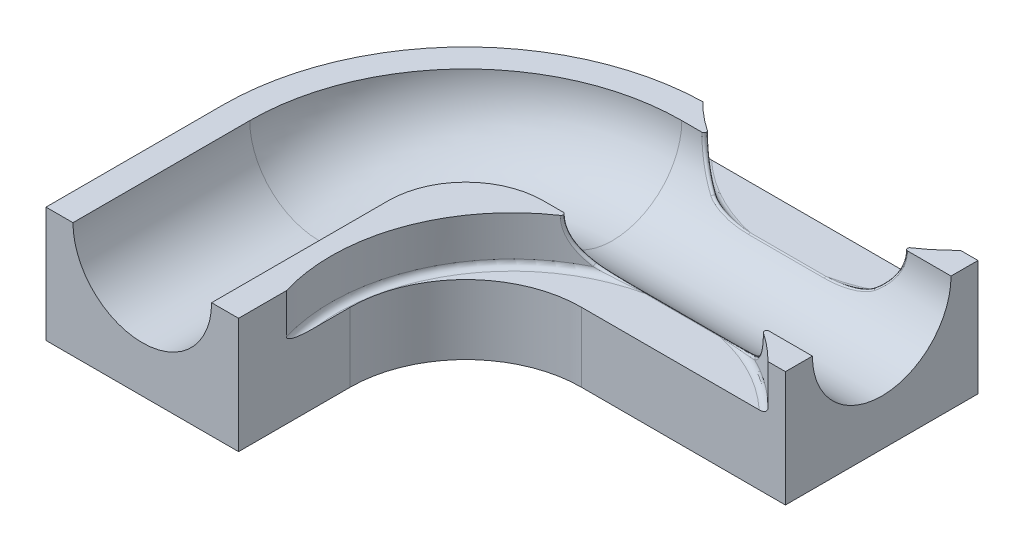
SolidWorks part; units mm, degrees
material "PLA"
ref_plane "前视基准面" through (0, 0, 0) normal (0, 0, 1) x (1, 0, 0)
ref_plane "上视基准面" through (0, 0, 0) normal (0, 1, 0) x (1, 0, 0)
ref_plane "右视基准面" through (0, 0, 0) normal (1, 0, 0) x (0, 0, -1)
sketch "草图1" plane through (0, 0, 0) normal (0, 1, 0) x (1, 0, 0)
  line L0 (0, 0) -> (-34.9545, 0) construction
  line L1 (-54, -19.0455) -> (-54, -42) construction
  line L2 (-66.5, -42) -> (-41.5, -42)
  line L3 (-41.5, -42) -> (-41.5, -27.5)
  line L4 (-66.5, -42) -> (-66.5, -19.0455)
  line L5 (-34.9545, 12.5) -> (0, 12.5)
  line L6 (0, 12.5) -> (0, -12.5)
  line L7 (0, -12.5) -> (-26.5, -12.5)
  circle A0 centre (-19, -29) radius 22.5 construction
  arc A1 (-54, -19.0455) -> (-34.9545, 0) centre (-34.9545, -19.0455) cw construction
  arc A2 (-66.5, -19.0455) -> (-34.9545, 12.5) centre (-34.9545, -19.0455) cw
  circle A4 centre (-29.9545, 0) radius 8.5 construction
  arc A5 (-26.5, -12.5) -> (-41.5, -27.5) centre (-26.5, -27.5) ccw
  point P13 (-54, -42)
  dimension "D1" = 45
  dimension "D2" = 29
  dimension "D7" = 17
  dimension "D9" = 15
  dimension "D3" = 19
  dimension "D4" = 35
  dimension "D6" = 25
  dimension "D5" = 13
  dimension "D8" = 5
  dimension "D10" = 31
extrude "凸台-拉伸1" add sketch "草图1" along normal blind 15
sketch "草图2" plane through (0, 0, 42) normal (0, 0, 1) x (1, 0, 0)
  line L0 (-66.5, 15) -> (-41.5, 15) construction
  circle A0 centre (-54, 15) radius 9
  dimension "D1" = 18
sketch "草图3" plane through (0, 15, 0) normal (0, 1, 0) x (1, 0, 0)
  line L0 (-54, -42) -> (-54, -19.0455)
  line L1 (-63, -42) -> (-45, -42) construction
  line L2 (-34.9545, 0) -> (0, 0)
  arc A0 (-54, -19.0455) -> (-34.9545, 0) centre (-34.9545, -19.0455) cw
  arc A3 (-34.9545, 12.5) -> (-66.5, -19.0455) centre (-34.9545, -19.0455) ccw construction
sweep "切除-扫描1" cut profiles "草图2" path "草图3"
sketch "草图4" plane through (0, 15, 0) normal (0, 1, 0) x (1, 0, 0)
  line L0 (-63, -42) -> (-45, -42) construction
  line L1 (-19, -29) -> (-19, 29) construction
  circle A0 centre (-19, -29) radius 23.5
  circle A1 centre (-19, 29) radius 23.5
  point P5 (-54, -42)
  dimension "D1" = 47
  dimension "D2" = 29
  dimension "D3" = 35
  dimension "D4" = 58
extrude "切除-拉伸1" cut sketch "草图4" against normal blind 6
fillet "圆角1" radius 0.8 4 edges at (-6.5722, 9, 9.0551) (-39.8662, 9, 18.1902) (-6.5722, 9, -9.0551) (-31.4222, 9, -9.0516)
fillet "圆角2" radius 0.3 10 edges at (-6.9805, 13.1432, 8.8064) (-13.1145, 9.0601, 6.7615) (-19, 9, 6.7082) (-27.1486, 9.4192, 7.0608) (-7.5699, 11.9488, -8.467) (-10.8514, 9.4192, -7.0608) (-19, 9, -6.7082) (-24.8855, 9.0601, -6.7615) (-30.4301, 11.9488, 8.467) (-31.0195, 13.1432, -8.8064)
sketch "草图5" plane through (0, 0, 0) normal (0, -1, 0) x (1, 0, 0)
  line L0 (-54, 42) -> (-54, 19.0455) construction
  line L1 (-66.5, 42) -> (-41.5, 42) construction
  line L2 (-34.9545, 0) -> (0, 0) construction
  line L3 (0, 12.5) -> (0, -12.5) construction
  arc A0 (-54, 19.0455) -> (-34.9545, 0) centre (-34.9545, 19.0455) ccw construction
  arc A1 (-66.5, 19.0455) -> (-34.9545, -12.5) centre (-34.9545, 19.0455) ccw construction
  circle A2 centre (-8, 9) radius 1.35
  circle A3 centre (-8, -9) radius 1.35
  circle A4 centre (-40, 13) radius 1.35
  circle A5 centre (-45, 32) radius 1.35
  circle A6 centre (-63, 32) radius 1.35
  dimension "D1" = 2.7
  dimension "D2" = 13
  dimension "D3" = 40
  dimension "D4" = 18
  dimension "D5" = 10
  dimension "D6" = 18
  dimension "D7" = 8
extrude "切除-拉伸2" cut sketch "草图5" against normal blind 5
